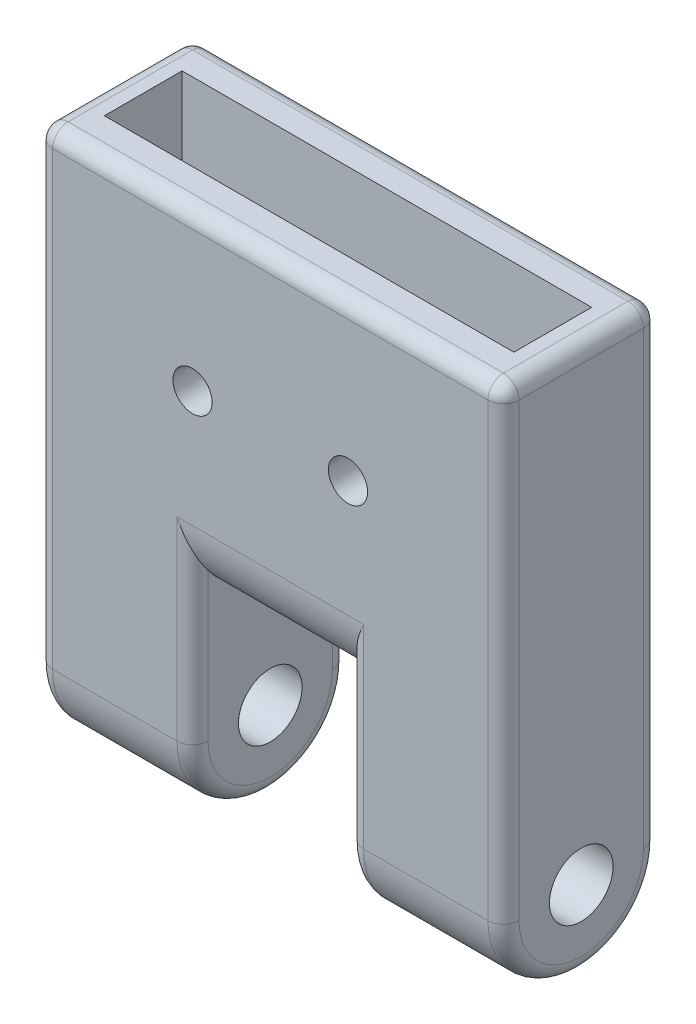
SolidWorks part; units mm, degrees
ref_plane "Front" through (0, 0, 0) normal (0, 0, 1) x (1, 0, 0)
ref_plane "Top" through (0, 0, 0) normal (0, 1, 0) x (1, 0, 0)
ref_plane "Right" through (0, 0, 0) normal (1, 0, 0) x (0, 0, -1)
sketch "Esquisse1" plane through (0, 0, 0) normal (0, 1, 0) x (1, 0, 0)
  line L1 (-19.05, 6.35) -> (19.05, 6.35)
  line L2 (-19.05, 6.35) -> (-19.05, -6.35)
  line L3 (-19.05, -6.35) -> (19.05, -6.35)
  line L4 (19.05, 6.35) -> (19.05, -6.35)
  line L5 (-19.05, 6.35) -> (19.05, -6.35) construction
  line L6 (-19.05, -6.35) -> (19.05, 6.35) construction
  point P0 (0, 0)
  dimension "D1" = 38.1
  dimension "D2" = 12.7
extrude "Boss.-Extru.1" add sketch "Esquisse1" along normal blind 3.175
sketch "Esquisse2" plane through (0, 3.175, 0) normal (0, 1, 0) x (1, 0, 0)
  line L0 (-19.05, -6.35) -> (19.05, -6.35) construction
  line L1 (-19.05, 6.35) -> (19.05, 6.35)
  line L2 (-19.05, 6.35) -> (-19.05, -6.35)
  line L3 (-19.05, -6.35) -> (19.05, -6.35)
  line L4 (19.05, 6.35) -> (19.05, -6.35)
  line L6 (-16.7259, 3.175) -> (16.7259, 3.175)
  line L7 (-16.7259, 3.175) -> (-16.7259, -3.175)
  line L8 (-16.7259, -3.175) -> (16.7259, -3.175)
  line L9 (16.7259, 3.175) -> (16.7259, -3.175)
  line L10 (-16.7259, 3.175) -> (16.7259, -3.175) construction
  line L11 (-16.7259, -3.175) -> (16.7259, 3.175) construction
  point P7 (0, 0)
  dimension "D1" = 33.4518
  dimension "D2" = 6.35
extrude "Boss.-Extru.2" add sketch "Esquisse2" along normal blind 25.4
sketch "Esquisse3" plane through (0, 0, 6.35) normal (0, 0, 1) x (1, 0, 0)
  line L0 (-6.35, 15.875) -> (6.35, 15.875) construction
  line L1 (-19.05, 28.575) -> (19.05, 28.575) construction
  circle A0 centre (-6.35, 15.875) radius 1.6
  circle A1 centre (6.35, 15.875) radius 1.6
  point P4 (0, 15.875)
  dimension "D1" = 3.2
  dimension "D2" = 3.2
  dimension "D3" = 12.7
  dimension "D4" = 12.7
extrude "Enlèv. mat.-Extru.1" cut sketch "Esquisse3" against normal blind 25.4
sketch "Esquisse4" plane through (19.05, 0, 0) normal (1, 0, 0) x (0, 0, -1)
  line L0 (-6.35, 0) -> (-6.35, -9.525)
  line L1 (6.35, -9.525) -> (6.35, 0)
  line L2 (6.35, 0) -> (-6.35, 0)
  arc A0 (-6.35, -9.525) -> (6.35, -9.525) centre (0, -9.525) ccw
  circle A1 centre (0, -9.525) radius 2.6
  dimension "D1" = 9.525
  dimension "D2" = 5.2
extrude "Boss.-Extru.3" add sketch "Esquisse4" against normal blind 12.7
mirror "Symétrie1" about plane through (0, 0, 0) normal (1, 0, 0) of "Boss.-Extru.3"
fillet "Congé1" radius 6.35 2 edges at (0, 0, -6.35) (0, 0, 6.35)
fillet "Congé2" radius 1.27 16 edges at (19.05, 9.525, -6.35) (19.05, -15.875, 0) (19.05, 9.525, 6.35) (-6.35, -1.5875, 6.35) (-6.35, -1.5875, -6.35) (-19.05, 9.525, -6.35) (-19.05, -15.875, 0) (6.35, -1.5875, -6.35) (6.35, -15.875, 0) (19.05, 28.575, 0) (0, 28.575, -6.35) (-19.05, 28.575, 0) (0, 28.575, 6.35) (-6.35, -15.875, 0) (-19.05, 9.525, 6.35) (6.35, -1.5875, 6.35)
